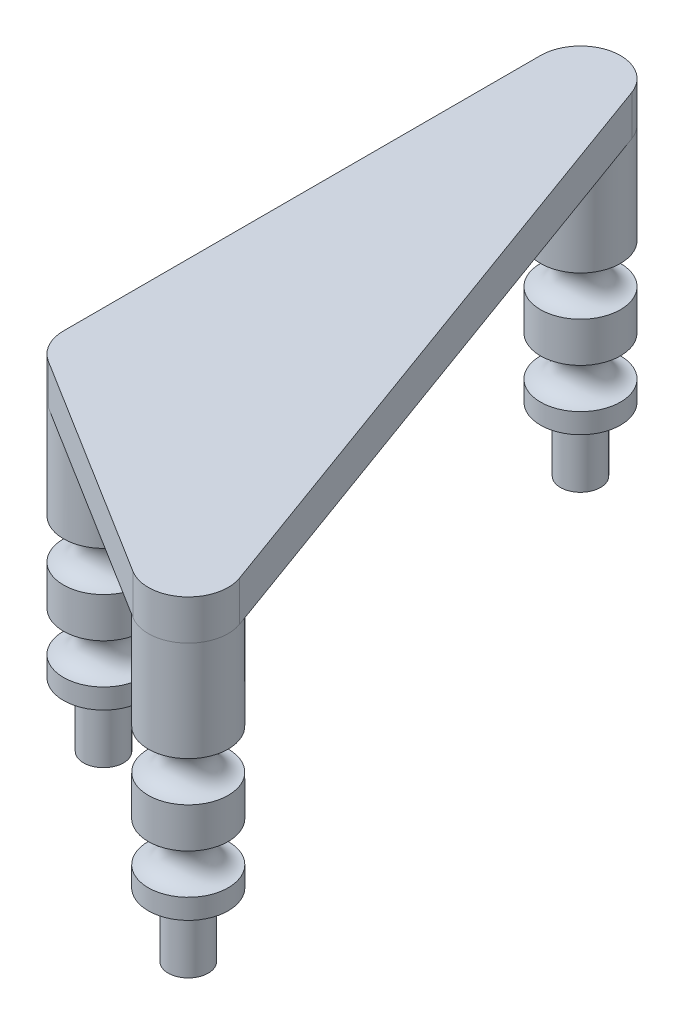
SolidWorks part; units mm, degrees
material "ABS"
ref_plane "Front Plane" through (0, 0, 0) normal (0, 0, 1) x (1, 0, 0)
ref_plane "Top Plane" through (0, 0, 0) normal (0, 1, 0) x (1, 0, 0)
ref_plane "Right Plane" through (0, 0, 0) normal (1, 0, 0) x (0, 0, -1)
sketch "Sketch1" plane through (0, 0, 0) normal (0, 1, 0) x (1, 0, 0)
  line L0 (0, 0) -> (0, 75.6844)
  line L1 (0, 75.6844) -> (35.6175, -22.1738)
  line L2 (35.6175, -22.1738) -> (0, 0)
  line L3 (-6.35, -3.5268) -> (-6.35, 111.697)
  line L4 (-6.35, 111.697) -> (47.8749, -37.2848)
  line L5 (47.8749, -37.2848) -> (-6.35, -3.5268)
  circle A0 centre (0, 75.6844) radius 6.35
  circle A1 centre (0, 0) radius 6.35
  circle A2 centre (35.6175, -22.1738) radius 6.35
  dimension "D5" = 12.7
  dimension "D6" = 12.7
  dimension "D7" = 12.7
  dimension "D1" = 20
  dimension "D2" = 75.6844
  dimension "D3" = 41.9557
  dimension "D4" = 6.35
extrude "Boss-Extrude1" add sketch "Sketch1" along normal blind 6.35 contours A2 L2 A1 L5 | A2 L5 L4 | A2 L4 A0 L1 | A1 L0 A0 L3 | A0 L4 L3 | A2 L1 A0 L0 A1 L2 | A2 | A1 | A0 region at (-3.2479, 0, -37.8422) region at (12.008, 0, -18.4658) region at (16.0516, 0, 13.9093) region at (-2.7233, 0, -91.1291) region at (20.84, 0, -27.8586) region at (41.9947, 0, 30.0357)
extrude "Boss-Extrude2" add sketch "Sketch1<4>" against normal blind 38.1 contours A0 | A1 | A2
sketch "Sketch1<4>" plane through (0, 0, 0) normal (0, 1, 0) x (1, 0, 0) same geometry as "Sketch1"
fillet "Fillet1" radius 6.35 2 edges at (47.8749, 3.175, 37.2848) (-6.35, 3.175, -111.697)
sketch "Sketch3" plane through (0, -38.1, 0) normal (0, -1, 0) x (-1, 0, 0)
  circle A0 centre (0, 0) radius 3.175
  circle A1 centre (-35.6175, -22.1738) radius 3.175
  circle A2 centre (0, 75.6844) radius 3.175
  dimension "D1" = 6.35
extrude "Boss-Extrude3" add sketch "Sketch3" along normal blind 10.16
ref_axis "Axis1" through (35.6175, -38.1, 22.1738) along (0, 1, 0)
ref_plane "Plane1" through (35.6175, 0, 22.1738) normal (0.8489, 0, 0.5285) x (0, 1, 0)
sketch "Sketch4" plane through (35.6175, 0, 22.1738) normal (0.8489, 0, 0.5285) x (0, 1, 0)
  line L0 (0, 6.35) -> (-38.1, 6.35) construction
  line L1 (-38.1, 6.35) -> (-38.1, -6.35) construction
  circle A0 centre (-31.75, 6.35) radius 3.175
  circle A1 centre (-19.05, 6.35) radius 3.175
  dimension "D1" = 6.35
  dimension "D2" = 6.35
  dimension "D3" = 19.05
revolve "Cut-Revolve1" cut sketch "Sketch4" angle 360 about axis through (35.6175, -38.1, 22.1738) along (0, 1, 0)
ref_axis "Axis2" through (0, 6.35, 0) along (0, -1, 0)
ref_plane "Plane2" through (0, 0, 0) normal (-0.8489, 0, -0.5285) x (0, -1, 0)
sketch "Sketch5" plane through (0, 0, 0) normal (-0.8489, 0, -0.5285) x (0, -1, 0)
  line L0 (38.1, 6.35) -> (0, 6.35) construction
  line L1 (38.1, -6.35) -> (38.1, 6.35) construction
  circle A0 centre (31.75, 6.35) radius 3.175
  circle A1 centre (19.05, 6.35) radius 3.175
  dimension "D2" = 19.05
  dimension "D3" = 6.35
  dimension "D4" = 6.35
  dimension "D1" = 6.35
revolve "Cut-Revolve2" cut sketch "Sketch5" angle 360 about axis through (0, 6.35, 0) along (0, -1, 0)
ref_axis "Axis3" through (0, -38.1, -75.6844) along (0, 1, 0)
ref_plane "Plane3" through (-24.3245, 0, -66.831) normal (-0.342, 0, -0.9397) x (0, 1, 0)
sketch "Sketch6" plane through (-24.3245, 0, -66.831) normal (-0.342, 0, -0.9397) x (0, 1, 0)
  line L0 (0, 32.2356) -> (-38.1, 32.2356) construction
  line L1 (0, 32.2356) -> (-38.1, 32.2356) construction
  line L2 (-38.1, 32.2356) -> (-38.1, 19.5356) construction
  circle A0 centre (-31.75, 32.2356) radius 3.175
  circle A1 centre (-19.05, 32.2356) radius 3.175
  dimension "D1" = 6.35
  dimension "D2" = 19.05
  dimension "D3" = 6.35
  dimension "D4" = 6.35
revolve "Cut-Revolve3" cut sketch "Sketch6" angle 360 about axis through (0, -38.1, -75.6844) along (0, 1, 0)
